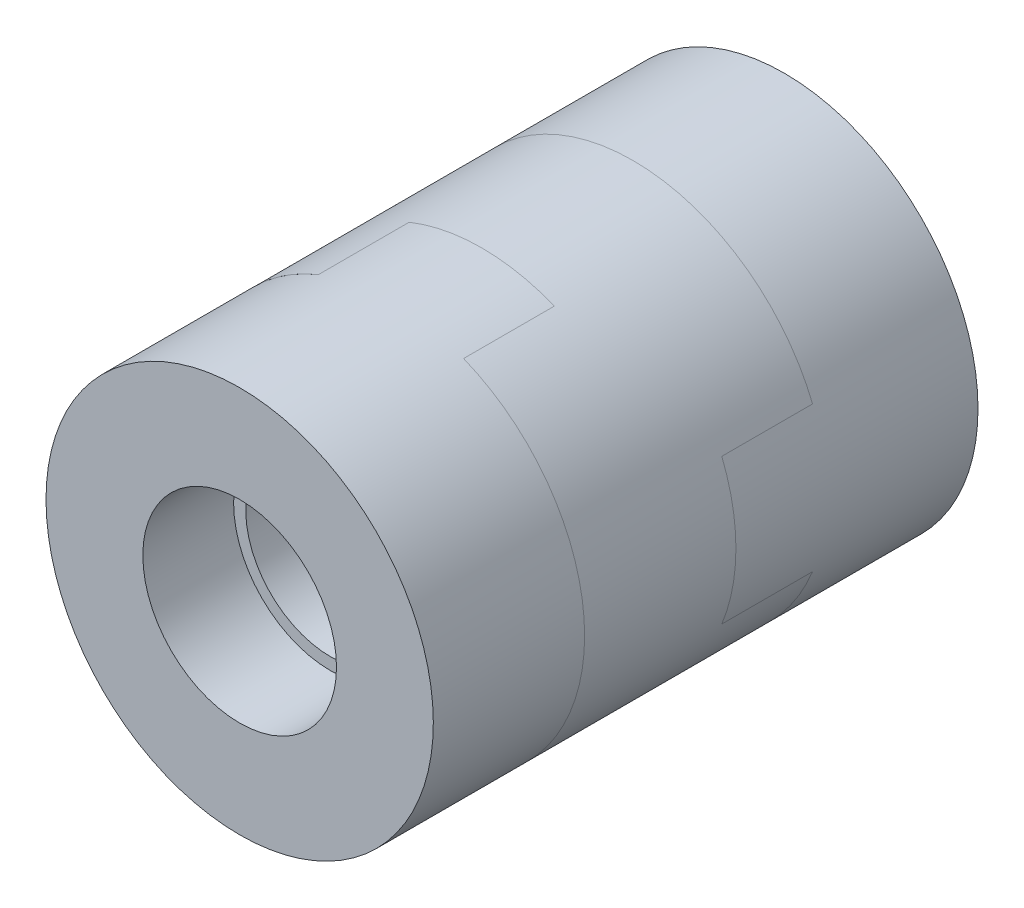
SolidWorks part; units mm, degrees
ref_plane "Front Plane" through (0, 0, 0) normal (0, 0, 1) x (1, 0, 0)
ref_plane "Top Plane" through (0, 0, 0) normal (0, 1, 0) x (1, 0, 0)
ref_plane "Right Plane" through (0, 0, 0) normal (1, 0, 0) x (0, 0, -1)
sketch "Croquis2" plane through (0, 0, 0) normal (0, 0, 1) x (1, 0, 0)
  circle A0 centre (0, 0) radius 16
  circle A1 centre (0, 0) radius 7
extrude "Saliente-Extruir1" add sketch "Croquis2" along normal blind 12.5
sketch "Croquis3" plane through (0, 0, 12.5) normal (0, 0, 1) x (1, 0, 0)
  line L0 (-14.8324, 6) -> (-3.6056, 6)
  line L1 (-14.8324, -6) -> (-3.6056, -6)
  line L2 (3.6056, 6) -> (14.8324, 6)
  line L3 (3.6056, -6) -> (14.8324, -6)
  arc A0 (-14.8324, 6) -> (-14.8324, -6) centre (0, 0) ccw
  arc A1 (-3.6056, 6) -> (-3.6056, -6) centre (0, 0) ccw
  arc A2 (14.8324, -6) -> (14.8324, 6) centre (0, 0) ccw
  arc A3 (3.6056, -6) -> (3.6056, 6) centre (0, 0) ccw
  dimension "D1" = 6
  dimension "D2" = 6
extrude "Saliente-Extruir2" add sketch "Croquis3" along normal blind 7.5
sketch "Croquis4" plane through (0, 0, 12.5) normal (0, 0, 1) x (1, 0, 0)
  line L0 (-14.8324, 6) -> (-3.6056, 6)
  line L1 (14.8324, -6) -> (3.6056, -6)
  line L2 (3.6056, 6) -> (14.8324, 6)
  line L3 (-3.6056, -6) -> (-14.8324, -6)
  arc A0 (-14.8324, -6) -> (14.8324, -6) centre (0, 0) ccw
  arc A1 (-3.6056, -6) -> (3.6056, -6) centre (0, 0) ccw
  arc A2 (3.6056, 6) -> (-3.6056, 6) centre (0, 0) ccw
  arc A3 (14.8324, 6) -> (-14.8324, 6) centre (0, 0) ccw
extrude "Saliente-Extruir3" add sketch "Croquis4" along normal blind 7.5 separate body
sketch "Croquis5" plane through (0, 0, 20) normal (0, 0, 1) x (1, 0, 0)
  circle A0 centre (0, 0) radius 16
  circle A1 centre (0, 0) radius 7
extrude "Saliente-Extruir5" add sketch "Croquis5" along normal blind 5 separate body
combine bodies "Combinar1" operation type add bodies to combine 103 106 104
sketch "Croquis6" plane through (0, 0, 25) normal (0, 0, 1) x (1, 0, 0)
  line L0 (-6, -14.8324) -> (-6, -3.6056)
  line L1 (6, -14.8324) -> (6, -3.6056)
  line L2 (-6, 3.6056) -> (-6, 14.8324)
  line L3 (6, 3.6056) -> (6, 14.8324)
  arc A0 (-6, 14.8324) -> (-6, -14.8324) centre (0, 0) ccw
  arc A1 (-6, 3.6056) -> (-6, -3.6056) centre (0, 0) ccw
  arc A2 (6, -3.6056) -> (6, 3.6056) centre (0, 0) ccw
  arc A3 (6, -14.8324) -> (6, 14.8324) centre (0, 0) ccw
  dimension "D1" = 6
  dimension "D2" = 6
extrude "Saliente-Extruir7" add sketch "Croquis6" along normal blind 7.5
move or copy body "Sólido-Mover/Copiar6" bodies to move or copy 102 copy yes number of copies 1 translate (0, 0, 32.5) parameters "D1"=0, "D2"=0, "D3"=32.5
move or copy body "Sólido-Mover/Copiar8" bodies to move or copy 115 copy no rotation origin (0, 0, 42.5) rotation axis (0, 1, 0) rotation angle 180
move or copy body "Sólido-Mover/Copiar9" bodies to move or copy 117 copy no rotation origin (0, 0, 0) rotation axis (0, 0, 1) rotation angle 90
move or copy body "Sólido-Mover/Copiar10" bodies to move or copy 118 copy no translate (0, 0, -7.5) parameters "D1"=0, "D2"=0, "D3"=7.5
sketch "Croquis7" plane through (0, 0, 45) normal (0, 0, 1) x (1, 0, 0)
  circle A0 centre (0, 0) radius 8
extrude "Cortar-Extruir1" cut sketch "Croquis7" against normal blind 7.5
